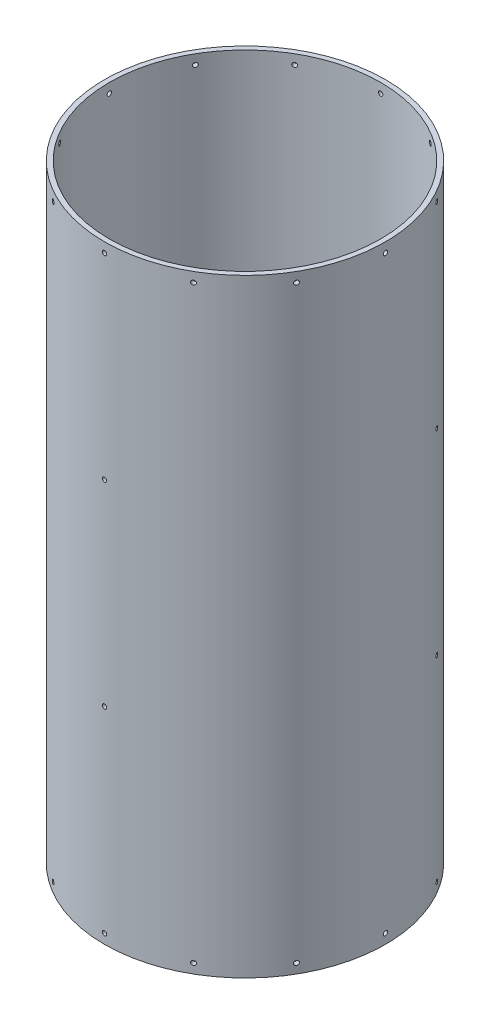
SolidWorks part; units mm, degrees
material "PVC Rigid"
ref_plane "Front Plane" through (0, 0, 0) normal (0, 0, 1) x (1, 0, 0)
ref_plane "Top Plane" through (0, 0, 0) normal (0, 1, 0) x (1, 0, 0)
ref_plane "Right Plane" through (0, 0, 0) normal (1, 0, 0) x (0, 0, -1)
sketch "Sketch1" plane through (0, 0, 0) normal (0, 1, 0) x (1, 0, 0)
  circle A0 centre (0, 0) radius 92.075
  circle A1 centre (0, 0) radius 88.9
  dimension "D1" = 184.15
  dimension "D2" = 177.8
extrude "Boss-Extrude1" add sketch "Sketch1" along normal mid plane 398.78
ref_plane "Plane1" through (0, 0, 92.075) normal (0, 0, 1) x (1, 0, 0)
sketch "Sketch3" plane through (0, 0, 92.075) normal (0, 0, 1) x (1, 0, 0)
  line L0 (0, -55) -> (0, 55) construction
  line L1 (-92.075, -199.39) -> (92.075, -199.39) construction
  circle A0 centre (0, -193.04) radius 1.4351
  dimension "D1" = 2.8702
  dimension "D2" = 6.35
extrude "Cut-Extrude1" cut sketch "Sketch3" against normal blind 19.304
pattern_circular "CirPattern1" count 12 over 360 about axis through (0, 199.39, 0) along (0, -1, 0) of "Cut-Extrude1" reverse direction yes
mirror "Mirror1" about plane through (0, 0, 0) normal (0, 1, 0) of "CirPattern1", "Cut-Extrude1"
sketch "Sketch4" plane through (0, 0, 92.075) normal (0, 0, 1) x (1, 0, 0)
  line L0 (0, -55) -> (0, 55) construction
  circle A0 centre (0, 64.3636) radius 1.4351
  circle A1 centre (0, -64.3636) radius 1.4351
  circle A2 centre (0, 193.04) radius 1.4351 construction
  circle A3 centre (0, -193.04) radius 1.4351 construction
  dimension "D1" = 128.6764
  dimension "D2" = 128.6764
  dimension "D3" = 2.8702
  dimension "D4" = 2.8702
extrude "Cut-Extrude2" cut sketch "Sketch4" against normal blind 43.18
pattern_circular "CirPattern2" count 3 over 360 about axis through (0, 199.39, 0) along (0, -1, 0) of "Cut-Extrude2"
